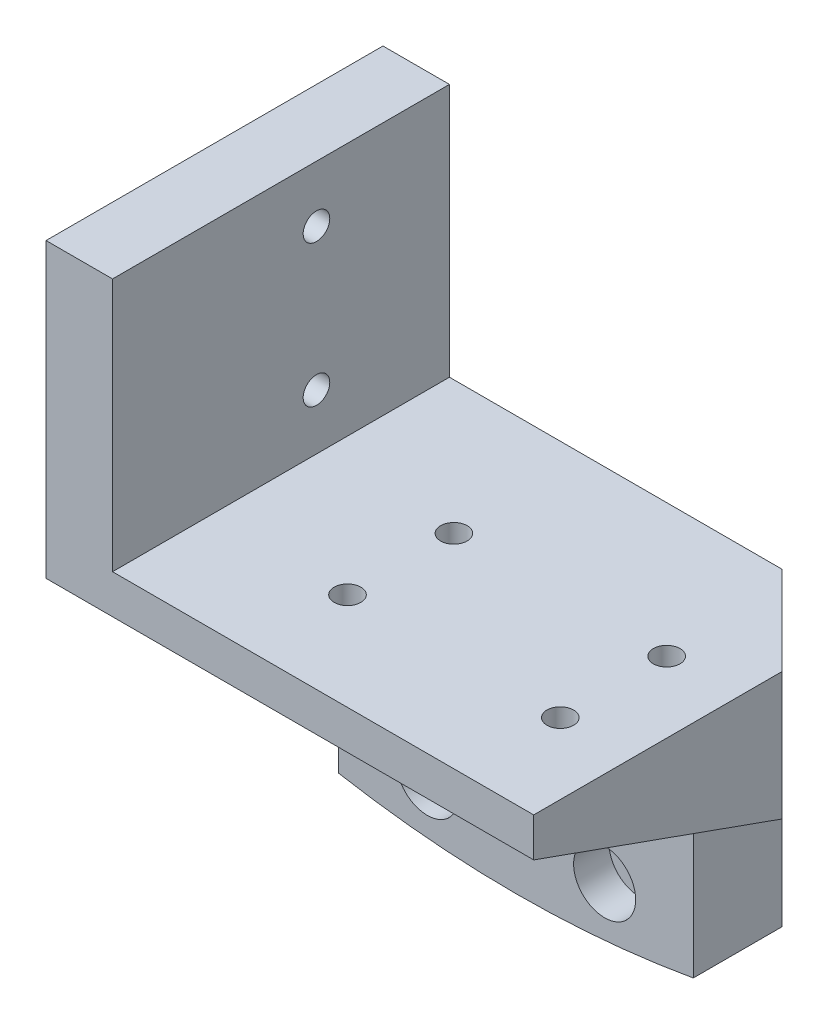
SolidWorks part; units mm, degrees
ref_plane "Plan de face" through (0, 0, 0) normal (0, 0, 1) x (1, 0, 0)
ref_plane "Plan de dessus" through (0, 0, 0) normal (0, 1, 0) x (1, 0, 0)
ref_plane "Plan de droite" through (0, 0, 0) normal (1, 0, 0) x (0, 0, -1)
sketch "Esquisse1" plane through (0, 0, 0) normal (0, 0, 1) x (1, 0, 0)
  line L0 (-20, -112.2319) -> (-20, -91.7)
  line L1 (-20, -91.7) -> (20, -91.7)
  line L2 (20, -91.7) -> (20, -112.2319)
  arc A0 (20, -112.2319) -> (-20, -112.2319) centre (0, 0) cw
  point P4 (0, -114)
  dimension "D1" = 114
  dimension "D3" = 22.3
  dimension "D2" = 40
extrude "Boss.-Extru.1" add sketch "Esquisse1" along normal blind 10
sketch "Esquisse2" plane through (0, 0, 10) normal (0, 0, 1) x (1, 0, 0)
  line L0 (0, -91.7) -> (0, -114) construction
  line L1 (20, -91.7) -> (-20, -91.7) construction
  line L2 (-10, -97.85) -> (-10, -107.85) construction
  line L3 (-10, -107.85) -> (10, -107.85) construction
  arc A0 (-20, -112.2319) -> (20, -112.2319) centre (0, 0) ccw construction
  circle A1 centre (-10, -97.85) radius 1.75
  circle A2 centre (-10, -107.85) radius 1.75
  circle A3 centre (10, -97.85) radius 1.75
  circle A4 centre (10, -107.85) radius 1.75
  point P15 (-10, -102.85)
  point P16 (0, -102.85)
  point P17 (0, -107.85)
  dimension "D3" = 3.5
  dimension "D1" = 10
  dimension "D2" = 20
extrude "Enlèv. mat.-Extru.1" cut sketch "Esquisse2" against normal up to next
sketch "Esquisse4" plane through (0, 0, 10) normal (0, 0, 1) x (1, 0, 0)
  circle A0 centre (-10, -97.85) radius 3.5
  circle A1 centre (10, -97.85) radius 3.5
  circle A2 centre (10, -107.85) radius 3.5
  circle A3 centre (-10, -107.85) radius 3.5
  dimension "D1" = 7
extrude "Enlèv. mat.-Extru.2" cut sketch "Esquisse4" against normal blind 4
sketch "Esquisse5" plane through (0, -91.7, 0) normal (0, 1, 0) x (1, 0, 0)
  line L1 (-20, 0) -> (30, 0)
  line L2 (-20, 0) -> (-20, -38)
  line L3 (-20, -38) -> (30, -38)
  line L4 (30, 0) -> (30, -38)
  dimension "D1" = 50
  dimension "D2" = 38
extrude "Boss.-Extru.2" add sketch "Esquisse5" along normal blind 14.4
sketch "Esquisse6" plane through (0, -91.7, 0) normal (0, -1, 0) x (1, 0, 0)
  line L0 (20, 10) -> (-20, 10) construction
  line L1 (30, 38) -> (30, 0) construction
  circle A0 centre (-2, 27) radius 1.5
  circle A1 centre (22, 27) radius 1.5
  circle A2 centre (-2, 15) radius 1.5
  circle A3 centre (22, 15) radius 1.5
  dimension "D1" = 3
  dimension "D2" = 5
  dimension "D3" = 24
  dimension "D4" = 12
  dimension "D5" = 8
extrude "Enlèv. mat.-Extru.3" cut sketch "Esquisse6" against normal up to next
sketch "Esquisse7" plane through (0, -91.7, 0) normal (0, -1, 0) x (1, 0, 0)
  circle A0 centre (-2, 27) radius 3
  circle A1 centre (22, 27) radius 3
  circle A2 centre (22, 15) radius 3
  circle A3 centre (-2, 15) radius 3
  dimension "D1" = 6
extrude "Enlèv. mat.-Extru.4" cut sketch "Esquisse7" against normal offset from surface (9.4 mm away) 5 up to face at (22, -77.3, 28.5)
chamfer "Chanfrein1" distance 10 angle 45 1 edges at (30, -84.5, 0)
chamfer "Chanfrein2" distance 28 distance2 10 1 edges at (5, -91.7, 38) first distance on face at (-2, -91.7, 12)
sketch "Esquisse8" plane through (-20, 0, 0) normal (-1, 0, 0) x (0, 0, 1)
  line L0 (10, -91.7) -> (0, -91.7)
  line L1 (0, -77.3) -> (0, -112.2319) construction
  line L2 (0, -91.7) -> (0, -48.7)
  line L3 (0, -48.7) -> (38, -48.7)
  line L4 (38, -48.7) -> (38, -81.7)
  line L5 (38, -81.7) -> (10, -91.7)
  dimension "D1" = 43
extrude "Boss.-Extru.3" add sketch "Esquisse8" along normal blind 5
sketch "Esquisse9" plane through (-20, 0, 0) normal (1, 0, 0) x (0, 0, -1)
  line L4 (-38, -77.3) -> (0, -77.3)
  line L5 (0, -77.3) -> (0, -48.7)
  line L6 (0, -48.7) -> (-38, -48.7)
  line L7 (-38, -48.7) -> (-38, -77.3)
  line L8 (-38, -77.3) -> (0, -77.3)
  line L9 (0, -77.3) -> (0, -48.7)
  line L10 (0, -48.7) -> (-38, -48.7)
  line L11 (-38, -48.7) -> (-38, -77.3)
  dimension "D1" = 0
extrude "Boss.-Extru.4" add sketch "Esquisse9" along normal blind 2.5
chamfer "Chanfrein3" distance 5 angle 45 1 edges at (-20, -91.7, 5)
sketch "Esquisse10" plane through (-25, 0, 0) normal (-1, 0, 0) x (0, 0, 1)
  line L0 (38, -48.7) -> (0, -48.7) construction
  line L2 (13.5, -82.3) -> (16.5, -82.3) construction
  line L3 (13.5, -82.3) -> (16.5, -82.3) construction
  circle A0 centre (15, -55.05) radius 1.5
  circle A1 centre (15, -71.05) radius 1.5
  point P7 (15, -82.3)
  dimension "D1" = 3
  dimension "D2" = 16
  dimension "D3" = 6.35
extrude "Enlèv. mat.-Extru.5" cut sketch "Esquisse10" against normal up to next
sketch "Esquisse11" plane through (-25, 0, 0) normal (-1, 0, 0) x (0, 0, 1)
  circle A0 centre (15, -55.05) radius 3
  circle A1 centre (15, -71.05) radius 3
  dimension "D1" = 6
extrude "Enlèv. mat.-Extru.6" cut sketch "Esquisse11" against normal offset from surface (2.5 mm away) 5 up to face at (-17.5, -53.55, 15)
